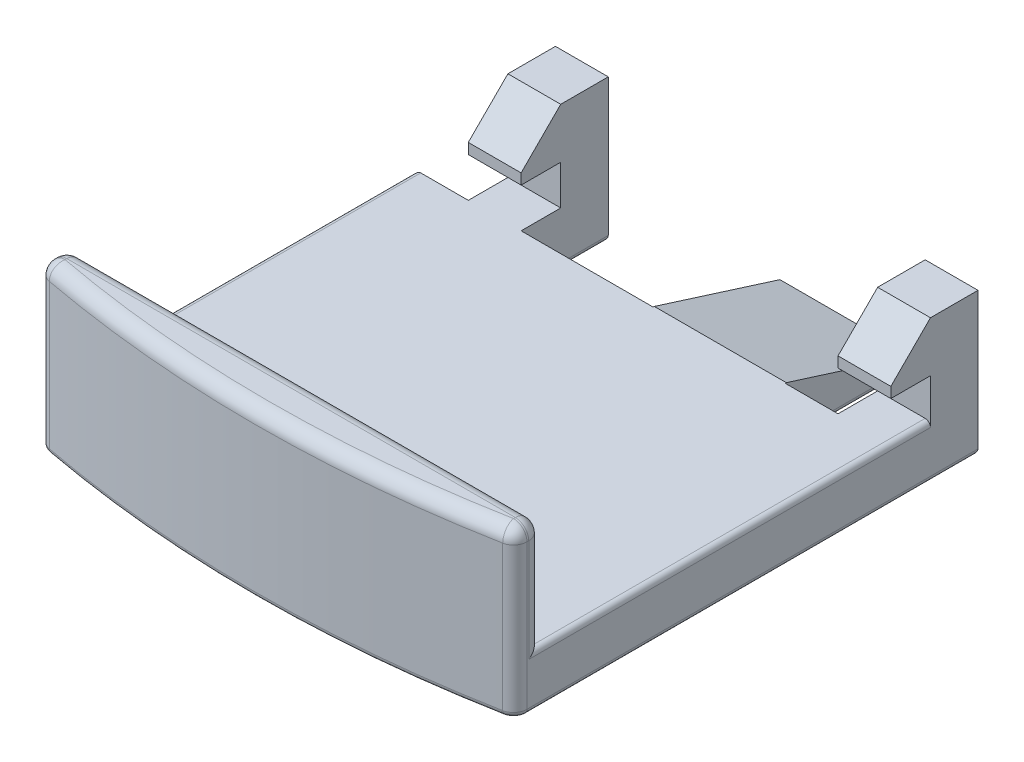
SolidWorks part; units mm, degrees
ref_plane "Front Plane" through (0, 0, 0) normal (0, 0, 1) x (1, 0, 0)
ref_plane "Top Plane" through (0, 0, 0) normal (0, 1, 0) x (1, 0, 0)
ref_plane "Right Plane" through (0, 0, 0) normal (1, 0, 0) x (0, 0, -1)
sketch "Sketch1" plane through (0, 0, 0) normal (0, 0, 1) x (1, 0, 0)
  line L0 (55, 0) -> (-55, 0) construction
  line L1 (-4.5, 0.5) -> (4.5, 0.5)
  line L2 (-4.5, 0.5) -> (-4.5, -0.5)
  line L3 (-4.5, -0.5) -> (4.5, -0.5)
  line L4 (4.5, 0.5) -> (4.5, -0.5)
  line L5 (0, -55) -> (0, 55) construction
  dimension "D1" = 1
  dimension "D2" = 0.5
  dimension "D3" = 9
  dimension "D4" = 4.5
extrude "Boss-Extrude1" add sketch "Sketch1" along normal mid plane 9
sketch "Sketch2" plane through (0, 0.5, 0) normal (0, 1, 0) x (1, 0, 0)
  line L0 (-4.5, -4.5) -> (4.5, -4.5)
  line L1 (-4.5, -4.5) -> (-4.5, -5)
  line L2 (4.5, -4.5) -> (4.5, -5)
  line L3 (-4.5, -4.5) -> (4.5, -4.5)
  arc A0 (-4.5, -5) -> (4.5, -5) centre (0, 17.8546) ccw
  line M3 (-4.5, -4.5) -> (4.5, -4.5)
  dimension "D1" = 0.5
  dimension "D2" = 0.5
extrude "Boss-Extrude2" add sketch "Sketch2" against normal up to surface (1 mm away) and the other way blind 2.1 contours L1 A0 L2 M3 region at (0, 0.5, 4.9073) up to face at (0, -0.5, 0)
fillet "Fillet1" radius 0.255 8 edges at (0, 2.6, 4.5) (4.5, 2.6, 4.75) (0, 2.6, 5.4388) (-4.5, 2.6, 4.75) (4.5, 1.05, 5) (-4.5, 1.05, 5)
sketch "Sketch3" plane through (0, 0.5, 0) normal (0, 1, 0) x (1, 0, 0)
  line L0 (4.5, 4.5) -> (-4.5, 4.5) construction
  line L1 (2.5, 5.5388) -> (3.5, 5.5388)
  line L2 (2.5, 5.5388) -> (2.5, 2.1)
  line L3 (2.5, 2.1) -> (3.5, 2.1)
  line L4 (3.5, 5.5388) -> (3.5, 2.1)
  line L5 (-2.5, 5.7131) -> (0, 5.7131)
  line L6 (-2.5, 5.7131) -> (-2.5, 2.1)
  line L7 (-2.5, 2.1) -> (0, 2.1)
  line L8 (0, 5.7131) -> (0, 2.1)
  line L9 (-5.9959, 5.9825) -> (-3.5, 5.9825)
  line L10 (-5.9959, 5.9825) -> (-5.9959, 2.1)
  line L11 (-5.9959, 2.1) -> (-3.5, 2.1)
  line L12 (-3.5, 5.9825) -> (-3.5, 2.1)
  line L13 (4.5, -4.755) -> (4.5, 4.5) construction
  line L14 (-4.5, -4.755) -> (-4.5, 4.5) construction
  dimension "D1" = 0
  dimension "D2" = 0
  dimension "D3" = 2.4
  dimension "D4" = 1
  dimension "D5" = 1
  dimension "D6" = 2.5
  dimension "D7" = 2.5
  dimension "D8" = 1
extrude "Cut-Extrude1" cut sketch "Sketch3" against normal blind 9
chamfer "Chamfer1" distance 0.75 angle 72.5 1 edges at (1.25, 0.5, -4.5) first distance on face at (1.25, 0, -4.5)
sketch "Sketch4" plane through (0, 0.5, 0) normal (0, 1, 0) x (1, 0, 0)
  line L0 (-3.5, 2.1) -> (-3.5, 4.5) construction
  line L1 (3.5, 4.5) -> (4.5, 4.5)
  line L2 (3.5, 4.5) -> (3.5, 2.1)
  line L3 (3.5, 2.1) -> (4.5, 2.1)
  line L4 (4.5, 4.5) -> (4.5, 2.1)
  line L5 (-2.5, 4.5) -> (-3.5, 4.5)
  line L6 (-2.5, 4.5) -> (-2.5, 2.1)
  line L7 (-2.5, 2.1) -> (-3.5, 2.1)
  line L8 (-3.5, 4.5) -> (-3.5, 2.1)
  line L9 (2.5, 2.1) -> (3.5, 2.1) construction
  line L10 (-2.5, 2.1) -> (0, 2.1) construction
  dimension "D1" = 0
  dimension "D2" = 0
extrude "Boss-Extrude3" add sketch "Sketch4" along normal blind 1.7
sketch "Sketch5" plane through (3.5, 0, 0) normal (-1, 0, 0) x (0, 0, 1)
  line L1 (-2.1, 0.5) -> (-2.85, 0.5)
  line L2 (-2.1, 0.5) -> (-2.1, 1.25)
  line L3 (-2.1, 1.25) -> (-2.85, 1.25)
  line L4 (-2.85, 0.5) -> (-2.85, 1.25)
  dimension "D1" = 0.75
  dimension "D2" = 0.75
extrude "Cut-Extrude2" cut sketch "Sketch5" against normal mid plane 21.7
chamfer "Chamfer2" distance 0.75 angle 45 2 edges at (-3, 2.2, -2.1) (4, 2.2, -2.1)
sketch "Sketch6" plane through (0, 2.2, 0) normal (0, 1, 0) x (1, 0, 0)
  line L0 (-2.5, 4.5) -> (-3.5, 4.5) construction
  line L1 (-5.6732, 5.449) -> (-1.7877, 5.449)
  line L2 (-5.6732, 5.449) -> (-5.6732, 3.75)
  line L3 (-5.6732, 3.75) -> (-1.7877, 3.75)
  line L4 (-1.7877, 5.449) -> (-1.7877, 3.75)
  line L5 (3.1912, 4.5921) -> (5.9392, 4.5921)
  line L6 (3.1912, 4.5921) -> (3.1912, 3.75)
  line L7 (3.1912, 3.75) -> (5.9392, 3.75)
  line L8 (5.9392, 4.5921) -> (5.9392, 3.75)
  line L9 (4.5, 4.5) -> (3.5, 4.5) construction
  dimension "D1" = 0.75
  dimension "D2" = 0.75
extrude "Cut-Extrude3" cut sketch "Sketch6" against normal blind 21.7
fillet "Fillet2" radius 0.1 19 edges at (-4.5, 0, -2.1) (3, -0.5, -2.1) (2.5, -0.5, -3.3) (1.25, -0.5, -4.5) (0, -0.5, -3.3) (-1.25, -0.5, -2.1) (-2.5, -0.5, -2.925) (-3, -0.5, -3.75) (-3.5, -0.5, -2.925) (-4, -0.5, -2.1) (-4.5, -0.5, 1.3447) (-4.4412, -0.5, 4.9522) (0, -0.5, 5.4388) (4.4412, -0.5, 4.9522) (4.5, -0.5, 0.5197) (4, -0.5, -3.75) (3.5, -0.5, -2.925)
